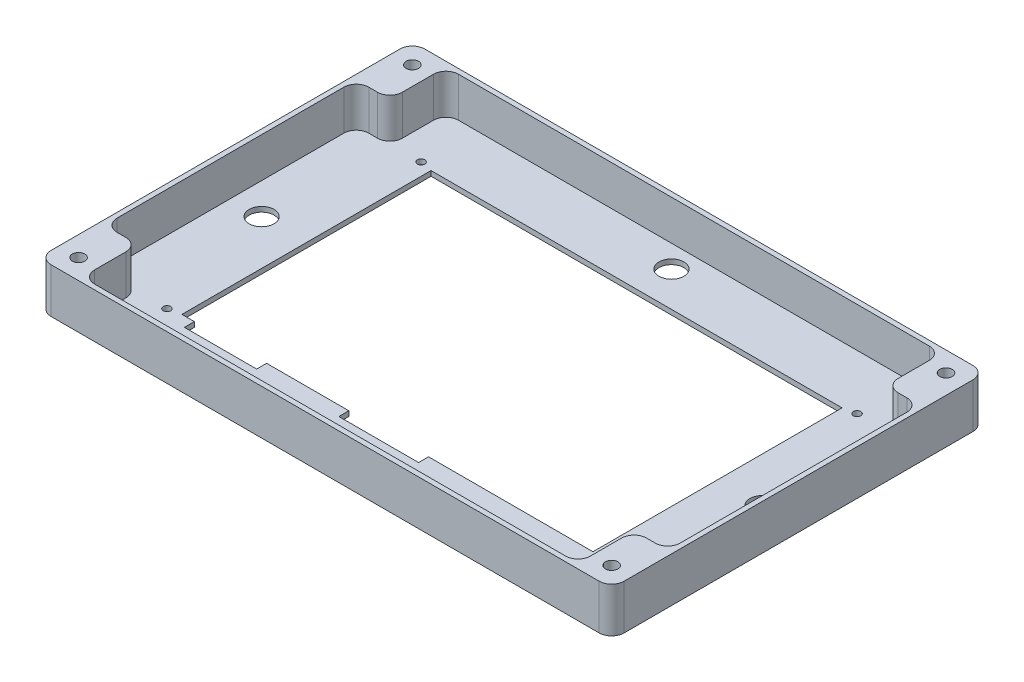
SolidWorks part; units mm, degrees
ref_plane "前视基准面" through (0, 0, 0) normal (0, 0, 1) x (1, 0, 0)
ref_plane "上视基准面" through (0, 0, 0) normal (0, 1, 0) x (1, 0, 0)
ref_plane "右视基准面" through (0, 0, 0) normal (1, 0, 0) x (0, 0, -1)
sketch "草图1" plane through (0, 0, 0) normal (0, 1, 0) x (1, 0, 0)
  line L1 (0, 0) -> (230, 0)
  line L2 (0, 0) -> (0, 150)
  line L3 (0, 150) -> (230, 150)
  line L4 (230, 0) -> (230, 150)
  dimension "D1" = 230
  dimension "D2" = 150
extrude "凸台-拉伸1" add sketch "草图1" along normal blind 18
sketch "草图2" plane through (0, 18, 0) normal (0, 1, 0) x (1, 0, 0)
  line L0 (0, 150) -> (0, 0) construction
  line L1 (0, 127.5) -> (13.5, 127.5)
  line L2 (0, 127.5) -> (0, 22.5)
  line L3 (0, 22.5) -> (13.5, 22.5)
  line L4 (230, 127.5) -> (230, 22.5)
  line L5 (230, 0) -> (230, 150) construction
  line L6 (230, 150) -> (0, 150) construction
  line L7 (13.5, 150) -> (216.5, 150)
  line L8 (13.5, 150) -> (13.5, 127.5)
  line L9 (13.5, 0) -> (216.5, 0)
  line L10 (216.5, 150) -> (216.5, 127.5)
  line L11 (0, 0) -> (230, 0) construction
  line L12 (216.5, 127.5) -> (230, 127.5)
  line L13 (13.5, 22.5) -> (13.5, 0)
  line L14 (216.5, 22.5) -> (216.5, 0)
  line L15 (216.5, 22.5) -> (230, 22.5)
  line L16 (2, 125.5) -> (2, 24.5)
  line L17 (2, 24.5) -> (15.5, 24.5)
  line L18 (15.5, 24.5) -> (15.5, 2)
  line L19 (15.5, 2) -> (214.5, 2)
  line L20 (214.5, 24.5) -> (214.5, 2)
  line L21 (214.5, 24.5) -> (228, 24.5)
  line L22 (228, 125.5) -> (228, 24.5)
  line L23 (214.5, 125.5) -> (228, 125.5)
  line L24 (214.5, 148) -> (214.5, 125.5)
  line L25 (15.5, 148) -> (214.5, 148)
  line L26 (15.5, 148) -> (15.5, 125.5)
  line L27 (2, 125.5) -> (15.5, 125.5)
  point P16 (115, 150)
  point P17 (0, 75)
  dimension "D1" = 203
  dimension "D2" = 105
  dimension "D3" = 2
extrude "切除-拉伸2" cut sketch "草图2" against normal blind 16 contours L16 L17 L18 L19 L20 L21 L22 L23 L24 L25 L26 L27
fillet "圆角1" radius 5 16 edges at (214.5, 10, -2) (214.5, 10, -24.5) (228, 10, -24.5) (228, 10, -125.5) (214.5, 10, -125.5) (214.5, 10, -148) (15.5, 10, -2) (15.5, 10, -24.5) (2, 10, -24.5) (2, 10, -125.5) (15.5, 10, -125.5) (15.5, 10, -148) (0, 9, 0) (230, 9, 0) (230, 9, -150) (0, 9, -150)
sketch "草图3" plane through (0, 18, 0) normal (0, 1, 0) x (1, 0, 0)
  line L0 (225, 150) -> (5, 150) construction
  line L2 (0, 145) -> (0, 5) construction
  line L3 (230, 5) -> (230, 145) construction
  line L4 (5, 0) -> (225, 0) construction
  circle A0 centre (8, 142) radius 2.5
  circle A1 centre (222.2146, 142) radius 2.5
  circle A2 centre (8, 8.0139) radius 2.5
  circle A3 centre (222, 8) radius 2.5
  dimension "D1" = 8
  dimension "D2" = 8
  dimension "D3" = 8
  dimension "D4" = 8
extrude "切除-拉伸4" cut sketch "草图3" against normal through all
sketch "草图5" plane through (0, 0, 0) normal (0, -1, 0) x (1, 0, 0)
  line L0 (5, 0) -> (225, 0) construction
  line L1 (32.5, -25) -> (197.5, -25)
  line L2 (32.5, -25) -> (32.5, -125)
  line L3 (32.5, -125) -> (197.5, -125)
  line L4 (197.5, -25) -> (197.5, -125)
  line L5 (0, -145) -> (0, -5) construction
  point P4 (115, -25)
  point P7 (115, 0)
  point P8 (32.5, -75)
  point P11 (0, -75)
  dimension "D1" = 100
  dimension "D2" = 165
extrude "切除-拉伸5" cut sketch "草图5" against normal through all contours L2 L1 L4 L3
sketch "草图6" plane through (0, 0, 0) normal (0, -1, 0) x (1, 0, 0)
  line L0 (5, 0) -> (225, 0) construction
  line L1 (26.5, -21) -> (203.5, -21)
  line L2 (24.5, -23) -> (24.5, -127)
  line L3 (26.5, -129) -> (203.5, -129)
  line L4 (205.5, -23) -> (205.5, -127)
  line L5 (0, -145) -> (0, -5) construction
  line L6 (37.5, -27.8134) -> (37.5, -16.3617) construction
  line L7 (66.5, -27.8134) -> (66.5, -16.3617) construction
  line L8 (99.5, -27.8134) -> (99.5, -16.3617) construction
  line L9 (131.5, -27.8134) -> (131.5, -16.3617) construction
  line L10 (32.5, -25) -> (197.5, -25) construction
  line L11 (66.5, -25) -> (37.5, -25)
  line L12 (66.5, -25) -> (66.5, -21)
  line L13 (66.5, -21) -> (37.5, -21)
  line L14 (37.5, -25) -> (37.5, -21)
  line L15 (32.5, -25) -> (197.5, -25) construction
  line L16 (131.5, -25) -> (99.5, -25)
  line L17 (131.5, -25) -> (131.5, -21)
  line L18 (131.5, -21) -> (99.5, -21)
  line L19 (99.5, -25) -> (99.5, -21)
  arc A5 (26.5, -21) -> (24.5, -23) centre (26.5, -23) ccw
  arc A6 (24.5, -127) -> (26.5, -129) centre (26.5, -127) ccw
  arc A7 (203.5, -129) -> (205.5, -127) centre (203.5, -127) ccw
  arc A8 (203.5, -21) -> (205.5, -23) centre (203.5, -23) cw
  point P4 (115, -21)
  point P7 (115, 0)
  point P8 (24.5, -75)
  point P11 (0, -75)
  point P36 (24.5, -21)
  point P39 (24.5, -129)
  point P44 (205.5, -21)
  line M15 (32.5, -25) -> (197.5, -25)
  dimension "D5" = 75
  dimension "D7" = 2
  dimension "D8" = 2
  dimension "D1" = 108
  dimension "D2" = 181
  dimension "D3" = 13
  dimension "D4" = 42
  dimension "D6" = 107
sketch "草图7" plane through (0, 0, 0) normal (0, -1, 0) x (1, 0, 0)
  line L0 (24.5, -23) -> (24.5, -127) construction
  line L1 (26.5, -21) -> (203.5, -21) construction
  line L2 (205.5, -23) -> (205.5, -127) construction
  line L3 (26.5, -129) -> (203.5, -129) construction
  circle A0 centre (27.5, -24) radius 1.5
  circle A1 centre (202.5, -126) radius 1.5
  circle A2 centre (27.5, -126) radius 1.5
  circle A3 centre (202.5, -24) radius 1.5
  point P14 (202.5, -24.5356)
  point P17 (103.919, -63.5518)
  point P18 (29.5054, -127)
  point P19 (0, 0)
  point P20 (0, 0)
  point P21 (0, 0)
  point P22 (0, 0)
  dimension "D3" = 3
  dimension "D4" = 3
  dimension "D7" = 3
  dimension "D8" = 3
  dimension "D1" = 3
  dimension "D2" = 3
  dimension "D5" = 3
  dimension "D6" = 3
extrude "切除-拉伸8" cut sketch "草图7" against normal up to next
sketch "草图8" plane through (0, 0, 0) normal (0, -1, 0) x (1, 0, 0)
  line L2 (32.5, -25) -> (32.5, -125) construction
  line L3 (32.5, -25) -> (197.5, -25) construction
  line L4 (24.5, -23) -> (24.5, -127) construction
  line L5 (205.5, -23) -> (205.5, -127) construction
  line L6 (26.5, -21) -> (203.5, -21) construction
  line L7 (26.5, -129) -> (203.5, -129) construction
  circle A0 centre (14.5, -75) radius 5
  circle A1 centre (115, -11) radius 5
  circle A2 centre (215.5, -75) radius 5
  circle A3 centre (115, -139) radius 5
  point P2 (0, 0)
  point P5 (105.2736, -11.6584)
  point P10 (0, 0)
  point P11 (0, 0)
  point P12 (121.2977, -10.7074)
  point P13 (12.3471, -71.4294)
  point P14 (15.509, -70.4166)
  point P17 (32.5, -75)
  point P18 (120.004, -11.3174)
  point P19 (130.5667, -143.8374)
  point P20 (14.1048, -75)
  point P21 (220.7368, -75)
  point P22 (0, 0)
  point P25 (115, -25)
  dimension "D1" = 10
  dimension "D5" = 10
  dimension "D6" = 10
  dimension "D7" = 10
  dimension "D8" = 10
  dimension "D2" = 10
  dimension "D3" = 10
  dimension "D4" = 10
extrude "切除-拉伸9" cut sketch "草图8" against normal up to next
extrude "切除-拉伸10" cut sketch "草图6" against normal up to next contours L14 L12 L1 M15 region at (52, 0, -23)
extrude "切除-拉伸11" cut sketch "草图6<3>" against normal up to next and the other way through all contours L19 L17 L1 M15 region at (115.5, 0, -23)
sketch "草图6<3>" plane through (0, 0, 0) normal (0, -1, 0) x (1, 0, 0) same geometry as "草图6"
